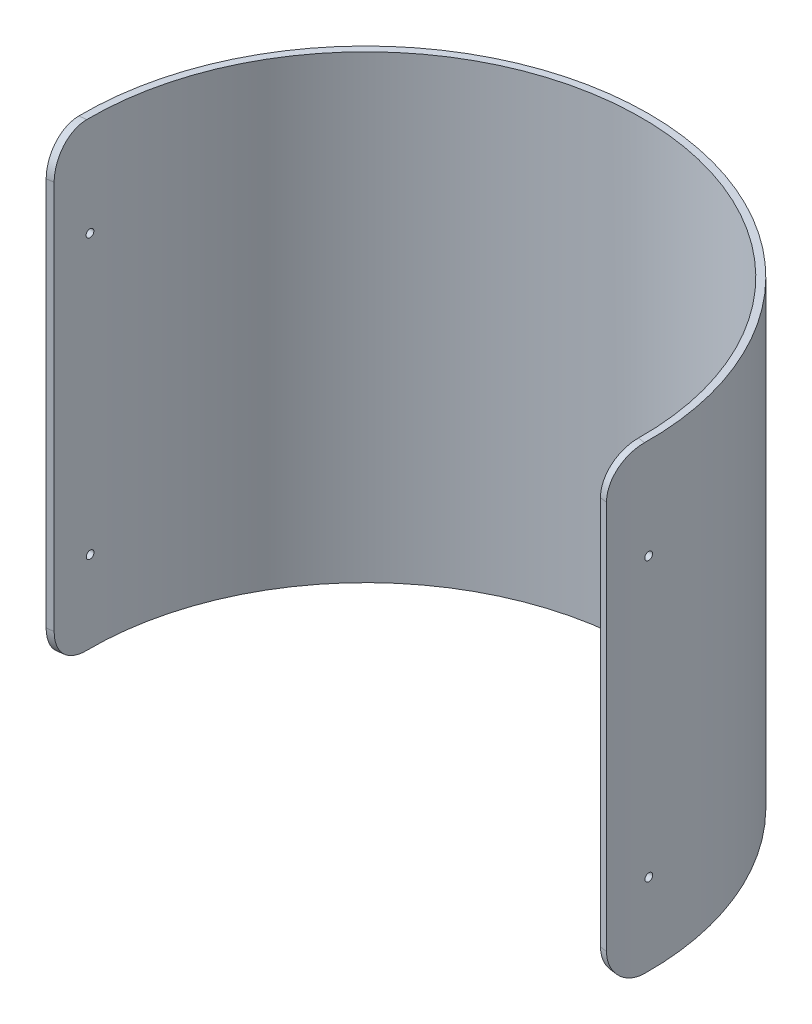
SolidWorks part; units mm, degrees
material "E-Glass Fiber"
ref_plane "Front Plane" through (0, 0, 0) normal (0, 0, 1) x (1, 0, 0)
ref_plane "Top Plane" through (0, 0, 0) normal (0, 1, 0) x (1, 0, 0)
ref_plane "Right Plane" through (0, 0, 0) normal (1, 0, 0) x (0, 0, -1)
sketch "Sketch1" plane through (0, 0, 0) normal (0, 1, 0) x (1, 0, 0)
  circle A0 centre (0, 0) radius 99.06
  circle A1 centre (0, 0) radius 101.6
  dimension "D1" = 203.2
  dimension "D2" = 198.12
extrude "Boss-Extrude1" add sketch "Sketch1" along normal blind 165.1
sketch "Sketch2" plane through (0, 0, 0) normal (0, 1, 0) x (1, 0, 0)
  line L0 (0, 0) -> (-100.6112, -14.14)
  line L1 (0, 0) -> (100.6112, -14.14)
  line L2 (0, 0) -> (0, 101.6) construction
  circle A0 centre (0, 0) radius 101.6 construction
  circle A1 centre (0, 0) radius 101.6
  circle A2 centre (0, 0) radius 99.06 construction
  circle A3 centre (0, 0) radius 99.06
  dimension "D1" = 98
extrude "Cut-Extrude1" cut sketch "Sketch2" along normal blind 165.1 contours A3 L0 A1 L1 region at (0, 0, 101.2555)
fillet "Fillet1" radius 12.7 4 edges at (99.3536, 0, 13.9632) (99.3536, 165.1, 13.9632) (-99.3536, 0, 13.9632) (-99.3536, 165.1, 13.9632)
sketch "Sketch3" plane through (0, 0, 0) normal (1, 0, 0) x (0, 0, -1)
  line L0 (-14.14, 150.8156) -> (-14.14, 2.4359)
  line L1 (-14.14, 152.4) -> (-14.14, 12.7) construction
  line L2 (0, 165.1) -> (0, 0) construction
  line L4 (-1.4527, 0) -> (10.5411, 0)
  line L5 (-1.4527, 0) -> (-1.4527, 177.8)
  line L6 (-1.4527, 177.8) -> (10.5411, 177.8)
  line L7 (10.5411, 0) -> (10.5411, 177.8)
  circle A0 centre (0.084, 147.828) radius 1.397
  circle A1 centre (0.0229, 129.1591) radius 1.397
  circle A2 centre (0.084, 29.1846) radius 1.397
  circle A3 centre (0, 9.8298) radius 1.397
  dimension "D7" = 2.794
  dimension "D8" = 2.794
  dimension "D9" = 2.794
  dimension "D10" = 2.794
  dimension "D1" = 29.972
  dimension "D2" = 14.224
  dimension "D3" = 177.8
  dimension "D4" = 18.669
  dimension "D5" = 137.9982
  dimension "D6" = 19.3548
extrude "Cut-Extrude2" cut sketch "Sketch3" against normal through all both and the other way through all contours A2 | A1 region at (0, 129.1591, -0.0229) region at (0, 29.1846, -0.084)
sketch "Sketch4" plane through (0, 0, 0) normal (0, 0, 1) x (1, 0, 0)
  circle A2 centre (0, 20.32) radius 9.525
  dimension "D1" = 19.05
  dimension "D2" = 20.32
extrude "Cut-Extrude3" cut sketch "Sketch4" against normal through all
